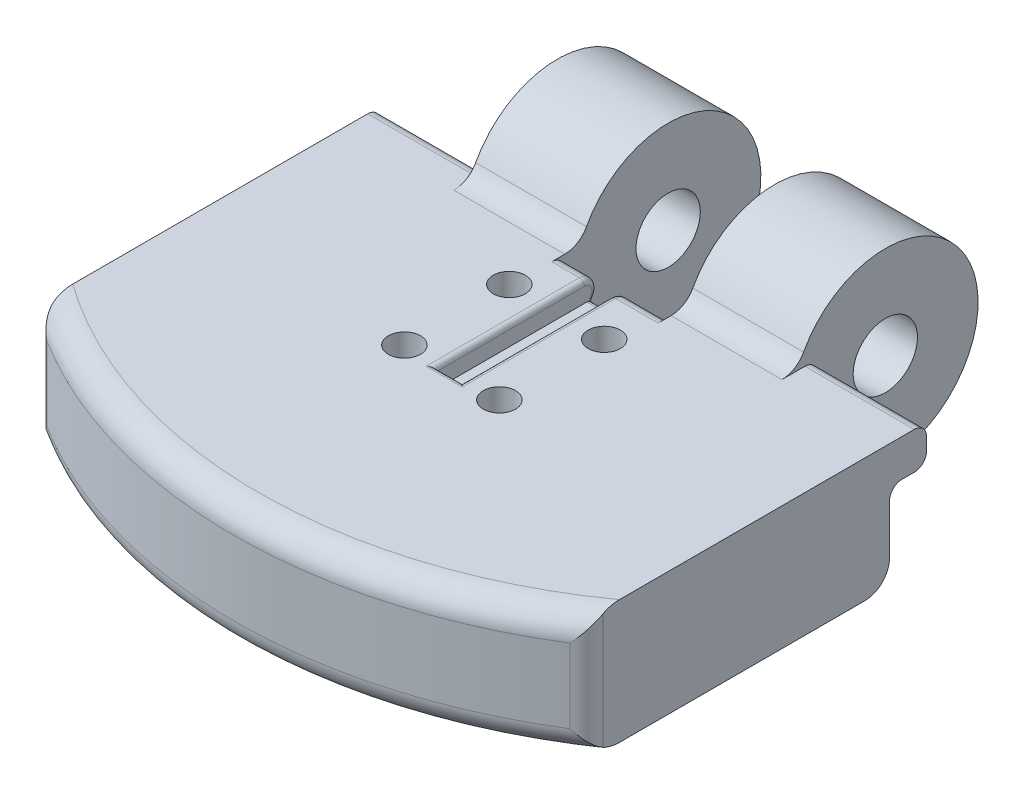
SolidWorks part; units mm, degrees
ref_plane "Front Plane" through (0, 0, 0) normal (0, 0, 1) x (1, 0, 0)
ref_plane "Top Plane" through (0, 0, 0) normal (0, 1, 0) x (1, 0, 0)
ref_plane "Right Plane" through (0, 0, 0) normal (1, 0, 0) x (0, 0, -1)
sketch "Sketch1" plane through (0, 0, 0) normal (0, 1, 0) x (1, 0, 0)
  line L1 (-28.575, 0) -> (28.575, 0)
  line L2 (-28.575, 0) -> (-28.575, -31.75)
  line L4 (28.575, 0) -> (28.575, -31.75)
  arc A0 (-28.575, -31.75) -> (28.575, -31.75) centre (0, 10.2513) ccw
  point P4 (0, 0)
  dimension "D3" = 50.8
  dimension "D1" = 57.15
  dimension "D2" = 31.75
extrude "Boss-Extrude1" add sketch "Sketch1" along normal blind 12.7
ref_plane "Plane1" through (-16.8402, 0, 0) normal (-1, 0, 0) x (0, 0, 1)
sketch "Sketch2" plane through (-16.8402, 0, 0) normal (-1, 0, 0) x (0, 0, 1)
  line L3 (0, 12.7) -> (31.75, 12.7) construction
  line L4 (0, 12.7) -> (-0.5447, 12.7)
  line L5 (0, 0) -> (-9.525, 0)
  line L6 (0, 12.7) -> (0, 0)
  line L7 (0, 0) -> (31.75, 0) construction
  arc A1 (-9.525, 0) -> (-0.5447, 12.7) centre (-9.525, 9.525) cw
  point P1 (0, 0)
  dimension "D1" = 9.525
  dimension "D2" = 0.5447
  dimension "D3" = 9.525
  dimension "D4" = 12.7
extrude "Boss-Extrude2" add sketch "Sketch2" against normal blind 11.3792
mirror "Mirror1" about plane through (0, 0, 0) normal (1, 0, 0) of "Boss-Extrude2"
sketch "Sketch4" plane through (5.461, 0, 0) normal (-1, 0, 0) x (0, 0, 1)
  circle A0 centre (-9.525, 9.525) radius 6.477
  dimension "D1" = 12.954
extrude "Cut-Extrude1" [suppressed] cut sketch "Sketch4" against normal blind 3.175
mirror "Mirror2" [suppressed] about plane through (0, 0, 0) normal (1, 0, 0)
sketch "Sketch5" plane through (-16.8402, 0, 0) normal (-1, 0, 0) x (0, 0, 1)
  circle A0 centre (-9.525, 9.525) radius 3.302
  dimension "D1" = 6.604
extrude "Cut-Extrude2" cut sketch "Sketch5" against normal through all
sketch "Sketch6" plane through (-28.575, 0, 0) normal (-1, 0, 0) x (0, 0, 1)
  line L2 (0, 7.9375) -> (0, 12.7)
  line L3 (0, 12.7) -> (4.7625, 12.7)
  arc A2 (0, 7.9375) -> (4.7625, 12.7) centre (0, 12.7) ccw
  dimension "D1" = 9.525
extrude "Cut-Extrude3" [suppressed] cut sketch "Sketch6" against normal blind 10.414
mirror "Mirror4" [suppressed] about plane through (0, 0, 0) normal (1, 0, 0)
sketch "Sketch7" plane through (0, 12.7, 0) normal (0, 1, 0) x (1, 0, 0)
  line L0 (-16.8402, 55) -> (-16.8402, -55) construction
  line L1 (-28.575, 0) -> (-16.8402, 0)
  line L2 (-28.575, 0) -> (-28.575, -1.27)
  line L3 (-28.575, -1.27) -> (-16.8402, -1.27)
  line L4 (-16.8402, 0) -> (-16.8402, -1.27)
  line L5 (0, 0) -> (0, -40.5487) construction
  line L6 (16.8402, 0) -> (16.8402, -1.27)
  line L7 (28.575, -1.27) -> (16.8402, -1.27)
  line L8 (28.575, 0) -> (28.575, -1.27)
  line L9 (28.575, 0) -> (16.8402, 0)
  arc A0 (-28.575, -31.75) -> (28.575, -31.75) centre (0, 10.2513) ccw construction
  dimension "D1" = 1.27
extrude "Cut-Extrude4" cut sketch "Sketch7" against normal through all
sketch "Sketch8" plane through (5.461, 0, 0) normal (-1, 0, 0) x (0, 0, 1)
  line L0 (0, 12.7) -> (0, 0)
  arc A0 (0, 12.7) -> (0, 0) centre (-7.0995, 6.35) cw
  dimension "D1" = 9.525
extrude "Cut-Extrude5" cut sketch "Sketch8" along normal up to surface (10.922 mm away) up to face at (-5.461, 9.525, -12.827)
fillet "Fillet3" radius 1.27 2 edges at (0, 0, 0) (0, 12.7, 0)
sketch "Sketch11" plane through (-28.575, 0, 0) normal (-1, 0, 0) x (0, 0, 1)
  line L1 (1.27, 0) -> (10.16, 0)
  line L2 (1.27, 0) -> (1.27, 5.08)
  line L3 (1.27, 5.08) -> (10.16, 5.08)
  line L4 (10.16, 0) -> (10.16, 5.08)
  dimension "D1" = 8.89
  dimension "D2" = 5.08
sketch "Sketch9" plane through (-28.575, 0, 0) normal (-1, 0, 0) x (0, 0, 1)
  line L0 (1.27, 0) -> (31.75, 0) construction
  line L1 (1.27, 0) -> (1.27, 12.7) construction
  line L2 (1.27, 12.7) -> (1.27, 0)
  arc A0 (1.27, 12.7) -> (1.27, 0) centre (-0.8973, 6.35) cw
  dimension "D1" = 6.7097
extrude "Cut-Extrude6" [suppressed] cut sketch "Sketch9" against normal blind 11.684
mirror "Mirror6" [suppressed] about plane through (0, 0, 0) normal (1, 0, 0)
fillet "Fillet7" [suppressed] radius 2.54
sketch "Sketch13" plane through (0, 12.7, 0) normal (0, 1, 0) x (1, 0, 0)
  circle A0 centre (-5.6151, -6.6346) radius 1.651
  circle A1 centre (4.1385, -6.6346) radius 1.651
  circle A2 centre (-5.6151, -17.4042) radius 1.651
  circle A3 centre (4.1385, -17.4042) radius 1.651
  dimension "D1" = 3.302
extrude "Cut-Extrude9" cut sketch "Sketch13" against normal through all
sketch "Sketch14" plane through (0, 0, 0) normal (0, -1, 0) x (1, 0, 0)
  circle A0 centre (-5.6151, 17.4042) radius 2.032
  circle A1 centre (4.1385, 17.4042) radius 2.032
  circle A2 centre (-5.6151, 6.6346) radius 2.032
  circle A3 centre (4.1385, 6.6346) radius 2.032
  dimension "D1" = 4.064
extrude "Cut-Extrude10" cut sketch "Sketch14" against normal blind 4.699
ref_plane "Plane2" through (0, 0, 1.27) normal (0, 0, -1) x (-1, 0, 0)
sketch "Sketch19" plane through (0, 0, 1.27) normal (0, 0, -1) x (-1, 0, 0)
  line L0 (-28.575, 0) -> (-28.575, 12.7) construction
  line L1 (-28.575, 12.7) -> (-16.8402, 12.7)
  line L2 (-28.575, 12.7) -> (-28.575, 8.89)
  line L3 (-28.575, 8.89) -> (-16.8402, 8.89)
  line L4 (-16.8402, 12.7) -> (-16.8402, 8.89)
  line L5 (-16.8402, 12.7) -> (-28.575, 12.7) construction
  line L6 (-16.8402, 19.05) -> (-16.8402, 0) construction
  dimension "D1" = 3.81
extrude "Boss-Extrude3" add sketch "Sketch19" along normal blind 3.81
mirror "Mirror8" about plane through (0, 0, 0) normal (1, 0, 0) of "Boss-Extrude3"
fillet "Fillet8" radius 1.27 2 edges at (-22.7076, 12.7, -2.54) (22.7076, 12.7, -2.54)
fillet "Fillet9" radius 1.27 4 edges at (-22.7076, 8.89, 1.27) (-22.7076, 8.89, -2.54) (22.7076, 8.89, 1.27) (22.7076, 8.89, -2.54)
fillet "Fillet10" radius 2.54 2 edges at (-22.7076, 0, 1.27) (22.7076, 0, 1.27)
sketch "Sketch20" plane through (0, 12.7, 0) normal (0, 1, 0) x (1, 0, 0)
  line L0 (-0.5317, -12.1485) -> (0.1987, 6.5664) construction
  line L1 (5.461, -1.1555) -> (-5.461, -1.1555) construction
  line L2 (-2.1061, -1.1555) -> (0.5768, -1.1555)
  line L8 (0.5768, -1.1555) -> (0.5768, -17.6655)
  line L9 (0.5768, -17.6655) -> (-2.1061, -17.6655)
  line L10 (-2.1061, -1.1555) -> (-2.1061, -17.6655)
  point P0 (-0.1027, -1.1555)
  point P1 (-1.2932, -12.1188)
  point P6 (0, 0)
  point P8 (0, 0)
  dimension "D1" = 16.51
  dimension "D2" = 0
  dimension "D3" = 2.6829
  dimension "D4" = 0.5768
extrude "Cut-Extrude11" cut sketch "Sketch20" against normal blind 2.032
fillet "Fillet11" radius 0.508 8 edges at (-2.1061, 12.0834, 1.3365) (0.5768, 12.0834, 1.3365) (-2.1061, 12.7, 10.0455) (-0.7647, 12.7, 17.6655) (0.5768, 12.7, 10.0455) (-2.1061, 10.7504, 1.3481) (0.5768, 10.7504, 1.3481) (-0.7647, 10.668, 1.3905)
sketch "Sketch23" plane through (0, 12.7, 0) normal (0, 1, 0) x (1, 0, 0)
  line L0 (0, 0) -> (0, -40.5487) construction
  line L1 (-28.575, 2.54) -> (-28.067, 2.54)
  line L2 (-28.575, 2.54) -> (-28.575, -32.0912)
  line L3 (-28.575, -32.0912) -> (-28.067, -32.0912)
  line L4 (-28.067, 2.54) -> (-28.067, -32.0912)
  line L5 (28.575, -32.0912) -> (28.067, -32.0912)
  line L6 (28.575, 2.54) -> (28.575, -32.0912)
  line L7 (28.067, 2.54) -> (28.067, -32.0912)
  line L8 (28.575, 2.54) -> (28.067, 2.54)
  arc A0 (-28.575, -31.75) -> (28.575, -31.75) centre (0, 10.2513) ccw construction
  dimension "D1" = 0.508
extrude "Cut-Extrude12" cut sketch "Sketch23" against normal through all
fillet "Fillet12" radius 2.54 4 edges at (0, 12.7, 40.5487) (0, 0, 40.5487) (-28.067, 6.35, 32.0912) (28.067, 6.35, 32.0912)
fillet "Fillet13" radius 2.54 2 edges at (11.1506, 12.7, -0.5447) (-11.1506, 12.7, -0.5447)
